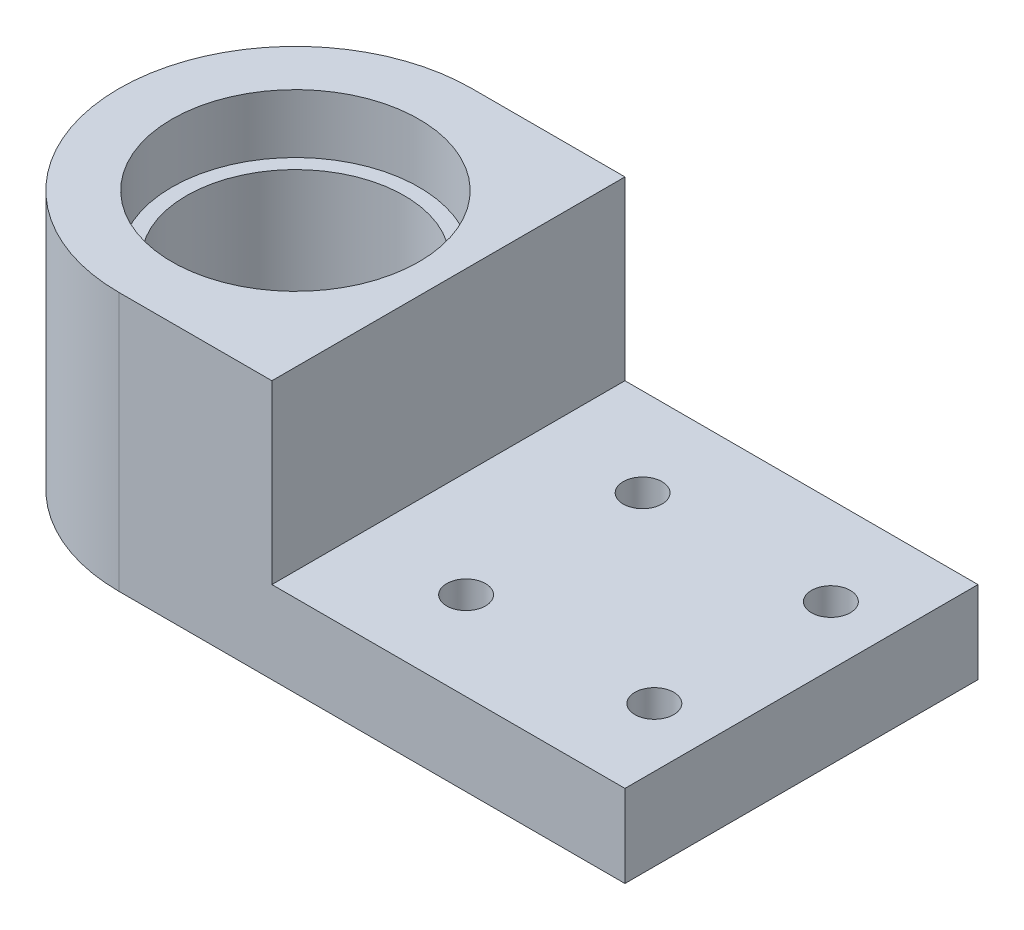
SolidWorks part; units mm, degrees
ref_plane "前视基准面" through (0, 0, 0) normal (0, 0, 1) x (1, 0, 0)
ref_plane "上视基准面" through (0, 0, 0) normal (0, 1, 0) x (1, 0, 0)
ref_plane "右视基准面" through (0, 0, 0) normal (1, 0, 0) x (0, 0, -1)
sketch "草图1" plane through (0, 0, 0) normal (0, 0, 1) x (1, 0, 0)
  line L0 (0, 0) -> (-116, 0)
  line L1 (-116, 0) -> (-116, 44)
  line L2 (-116, 44) -> (-60, 44)
  line L3 (-60, 44) -> (-60, 14)
  line L4 (-60, 14) -> (0, 14)
  line L5 (0, 14) -> (0, 0)
  dimension "D1" = 14
  dimension "D2" = 30
  dimension "D3" = 56
  dimension "D4" = 60
extrude "凸台-拉伸1" add sketch "草图1" along normal blind 60
fillet "圆角1" radius 30 2 edges at (-116, 22, 60) (-116, 22, 0)
sketch "草图2" plane through (0, 44, 0) normal (0, 1, 0) x (1, 0, 0)
  circle A0 centre (-86, -30) radius 21
  dimension "D1" = 42
extrude "切除-拉伸1" cut sketch "草图2" against normal blind 10 contours A0
sketch "草图3" plane through (0, 34, 0) normal (0, 1, 0) x (1, 0, 0)
  circle A0 centre (-86, -30) radius 18.5
  dimension "D1" = 37
extrude "切除-拉伸2" cut sketch "草图3" against normal through all both and the other way through all
sketch "草图4" plane through (0, 0, 0) normal (0, -1, 0) x (1, 0, 0)
  line L0 (0, 60) -> (0, 0) construction
  line L1 (-42, 15) -> (-10, 15) construction
  line L2 (-42, 15) -> (-42, 45) construction
  line L3 (-42, 45) -> (-10, 45) construction
  line L4 (-10, 15) -> (-10, 45) construction
  line L5 (-42, 15) -> (-10, 45) construction
  line L6 (-42, 45) -> (-10, 15) construction
  point P1 (-10, 45)
  point P2 (-42, 15)
  point P3 (-42, 45)
  point P4 (-10, 15)
  point P5 (0, 30)
  point P6 (-26, 30)
  dimension "D1" = 32
  dimension "D2" = 30
  dimension "D3" = 10
hole_wizard "M6 六角圆柱头螺钉的柱形沉头孔1" positions "草图4" profile "草图6" counterbore size "M6" standard "GB"
sketch "草图6" plane through (-10, 0, 45) normal (1, 0, 0) x (0, 0, -1)
  line L0 (0, 0) -> (0, 44)
  line L1 (0, 44) -> (3.3, 44)
  line L3 (3.3, 44) -> (3.3, 6.8)
  line L4 (3.3, 6.8) -> (5.5, 6.8)
  line L5 (5.5, 6.8) -> (5.5, 0)
  line L7 (5.5, 0) -> (0, 0)
  line L11 (0, -6.35) -> (0, 107.95) construction
  dimension "通孔孔直径" = 6.6
  dimension "通孔孔深度" = 44
  dimension "柱形沉头孔直径" = 11
  dimension "柱形沉头孔深度" = 6.8
